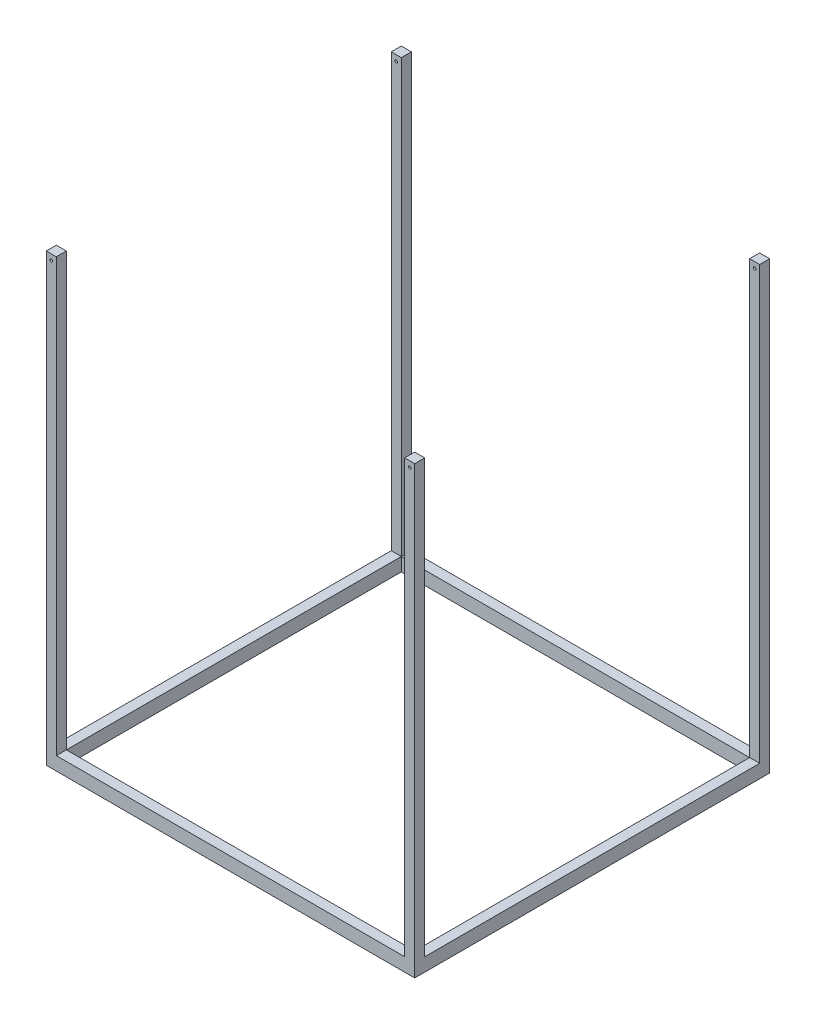
SolidWorks part; units mm, degrees
material "Galvanized Steel"
ref_plane "Front Plane" through (0, 0, 0) normal (0, 0, 1) x (1, 0, 0)
ref_plane "Top Plane" through (0, 0, 0) normal (0, 1, 0) x (1, 0, 0)
ref_plane "Right Plane" through (0, 0, 0) normal (1, 0, 0) x (0, 0, -1)
sketch "Sketch1" plane through (0, 0, 0) normal (0, 1, 0) x (1, 0, 0)
  line L0 (-660.4, 635) -> (-698.5, 635)
  line L1 (-698.5, -673.1) -> (698.5, -673.1)
  line L2 (-698.5, -673.1) -> (-698.5, 673.1)
  line L3 (-698.5, 673.1) -> (698.5, 673.1)
  line L4 (698.5, -673.1) -> (698.5, 673.1)
  line L5 (-698.5, -673.1) -> (698.5, 673.1) construction
  line L6 (-698.5, 673.1) -> (698.5, -673.1) construction
  line L7 (-660.4, -635) -> (660.4, -635)
  line L8 (-660.4, -635) -> (-660.4, 635)
  line L9 (-660.4, 635) -> (660.4, 635)
  line L10 (660.4, -635) -> (660.4, 635)
  line L11 (-660.4, -635) -> (660.4, 635) construction
  line L12 (-660.4, 635) -> (660.4, -635) construction
  line L13 (-660.4, 635) -> (-660.4, 673.1)
  line L14 (660.4, 635) -> (660.4, 673.1)
  line L15 (660.4, 635) -> (698.5, 635)
  line L16 (660.4, -635) -> (698.5, -635)
  line L17 (660.4, -635) -> (660.4, -673.1)
  line L18 (-660.4, -635) -> (-698.5, -635)
  line L19 (-660.4, -635) -> (-660.4, -673.1)
  point P0 (0, 0)
  point P6 (0, 0)
  dimension "D1" = 1320.8
  dimension "D2" = 1270
  dimension "D3" = 38.1
  dimension "D4" = 38.1
extrude "Boss-Extrude1" add sketch "Sketch1" along normal blind 50.8 contours L9 L14 L3 L13 | L18 L8 L0 L2 | L0 L13 L3 L2 | L19 L18 L2 L1 | L7 L19 L1 L17 | L16 L17 L1 L4 | L10 L16 L4 L15 | L14 L15 L4 L3 region at (-679.45, 0, 0) region at (0, 0, -654.05) region at (-679.45, 0, -654.05) region at (-679.45, 0, 654.05) region at (0, 0, 654.05) region at (679.45, 0, 0) region at (679.45, 0, -654.05) region at (679.45, 0, 654.05)
extrude "Boss-Extrude2" add sketch "Sketch1<3>" along normal blind 1689.1 contours L19 L18 L2 L1 | L0 L13 L3 L2 | L14 L15 L4 L3 | L16 L17 L1 L4 region at (-679.45, 0, -654.05) region at (-679.45, 0, 654.05) region at (679.45, 0, -654.05) region at (679.45, 0, 654.05)
sketch "Sketch1<3>" plane through (0, 0, 0) normal (0, 1, 0) x (1, 0, 0) same geometry as "Sketch1"
hole_wizard "3/8 Clearance Hole1" positions "Sketch2" profile "Sketch3" hole size "3/8" standard "ANSI Inch" end condition through all
sketch "Sketch2" plane through (0, 0, 673.1) normal (0, 0, 1) x (1, 0, 0)
  line L1 (-698.5, 1689.1) -> (-698.5, 0) construction
  line L2 (-698.5, 1689.1) -> (-660.4, 1689.1) construction
  point P0 (-679.45, 1666.936)
  point P3 (0, 0)
  dimension "D1" = 19.05
  dimension "D2" = 22.164
sketch "Sketch3" plane through (-679.45, 1666.936, 673.1) normal (1, 0, 0) x (0, -1, 0)
  line L0 (0, 0) -> (0, 1346.2)
  line L1 (0, 1346.2) -> (5.0419, 1346.2)
  line L2 (5.0419, 1346.2) -> (5.0419, 0)
  line L5 (5.0419, 0) -> (0, 0)
  line L11 (0, -6.35) -> (0, 107.95) construction
  dimension "Thru Hole Dia." = 10.0838
  dimension "Thru Hole Depth" = 1346.2
hole_wizard "3/8 Clearance Hole2" positions "Sketch4" profile "Sketch5" hole size "3/8" standard "ANSI Inch" end condition through all
sketch "Sketch4" plane through (0, 0, 673.1) normal (0, 0, 1) x (1, 0, 0)
  line L0 (698.5, 1689.1) -> (698.5, 0) construction
  line L1 (660.4, 1689.1) -> (698.5, 1689.1) construction
  point P0 (679.45, 1666.936)
  dimension "D1" = 19.05
  dimension "D2" = 22.164
sketch "Sketch5" plane through (679.45, 1666.936, 673.1) normal (1, 0, 0) x (0, -1, 0)
  line L0 (0, 0) -> (0, 1346.2)
  line L1 (0, 1346.2) -> (5.0419, 1346.2)
  line L2 (5.0419, 1346.2) -> (5.0419, 0)
  line L5 (5.0419, 0) -> (0, 0)
  line L11 (0, -6.35) -> (0, 107.95) construction
  dimension "Thru Hole Dia." = 10.0838
  dimension "Thru Hole Depth" = 1346.2
